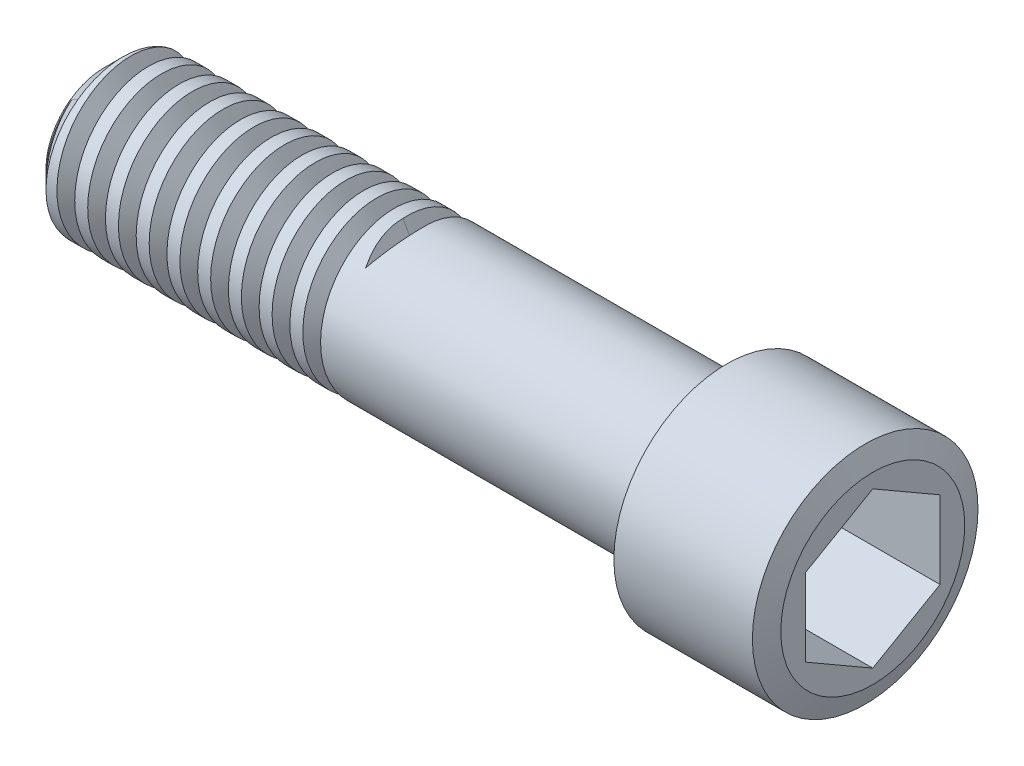
SolidWorks part; units mm, degrees
material "Cast Carbon Steel"
ref_plane "Front Plane" through (0, 0, 0) normal (0, 0, 1) x (1, 0, 0)
ref_plane "Top Plane" through (0, 0, 0) normal (0, 1, 0) x (1, 0, 0)
ref_plane "Right Plane" through (0, 0, 0) normal (1, 0, 0) x (0, 0, -1)
sketch "Sketch1" plane through (0, 0, 0) normal (0, 0, 1) x (1, 0, 0)
  line L0 (15.875, 0) -> (-15.875, 0) construction
  line L1 (-15.875, 0) -> (-15.875, 2.413)
  line L2 (-15.113, 3.175) -> (9.525, 3.175)
  line L3 (9.525, 3.175) -> (9.525, 5.5562)
  line L4 (9.8379, 6.4158) -> (15.5621, 6.4158)
  line L5 (15.875, 5.5562) -> (15.875, 0)
  line L6 (9.525, 5.5562) -> (9.8379, 6.4158)
  line L7 (15.5621, 6.4158) -> (15.875, 5.5562)
  line L8 (-15.875, 2.413) -> (-15.113, 3.175)
  line L9 (13.0969, 4.8119) -> (15.875, 6.4158) construction
  line L10 (15.875, 6.4158) -> (18.6531, 4.8119) construction
  line L11 (-15.875, 0) -> (15.875, 0)
  circle A0 centre (15.875, 0) radius 5.5563 construction
  point P4 (0, 0)
  point P5 (-15.875, 3.175)
  dimension "D8" = 11.1125
  dimension "D1" = 25.4
  dimension "D2" = 20
  dimension "D3" = 20
  dimension "D4" = 6.35
  dimension "D5" = 6.35
  dimension "D6" = 60
revolve "Revolve1" add sketch "Sketch1" angle 360 about L11
sketch "Sketch2" plane through (15.875, 0, 0) normal (1, 0, 0) x (0, 0, -1)
  line L1 (0, 6.4158) -> (-5.5562, 3.2079)
  line L2 (-5.5562, 3.2079) -> (-5.5562, -3.2079)
  line L3 (-5.5562, -3.2079) -> (0, -6.4158)
  line L4 (0, -6.4158) -> (5.5562, -3.2079)
  line L5 (5.5562, -3.2079) -> (5.5562, 3.2079)
  line L6 (5.5562, 3.2079) -> (0, 6.4158)
  circle A0 centre (0, 0) radius 5.5562 construction
  circle A1 centre (0, 0) radius 5.5563 construction
extrude "Cut-Extrude1" [suppressed] cut sketch "Sketch2" against normal through all flip side to cut
sketch "Sketch6" plane through (0, 0, 0) normal (0, 0, 1) x (1, 0, 0)
  line L0 (9.525, 0) -> (15.875, 0) construction
  line L1 (9.525, 3.175) -> (9.525, -3.175) construction
  line L2 (15.875, -5.5563) -> (15.875, 5.5562) construction
  line L3 (9.525, 3.8013) -> (9.8379, 4.6609)
  line L4 (9.525, 5.5562) -> (9.525, -5.5563) construction
  line L5 (9.8379, -6.4158) -> (9.8379, 6.4158) construction
  line L6 (9.8379, 4.6609) -> (15.5621, 4.6609)
  line L7 (15.5621, -6.4158) -> (15.5621, 6.4158) construction
  line L8 (15.5621, 4.6609) -> (15.875, 3.8013)
  line L9 (15.875, 3.8013) -> (15.875, 6.4158)
  line L10 (15.875, 6.4158) -> (9.525, 6.4158)
  line L11 (9.525, 6.4158) -> (9.525, 3.8013)
  line L12 (9.8379, 6.4158) -> (9.525, 5.5562) construction
  line L13 (15.875, 5.5562) -> (15.5621, 6.4158) construction
  line L14 (15.5621, 6.4158) -> (9.8379, 6.4158) construction
  dimension "D1" = 9.3218
revolve "Cut-Revolve1" cut sketch "Sketch6" angle 360 about L0
sketch "Sketch3" plane through (-15.875, 0, 0) normal (-1, 0, 0) x (0, 0, 1)
  circle A0 centre (0, 0) radius 3.175 construction
  circle A1 centre (0, 0) radius 3.175
curve "Helix/Spiral1" pitch 1.27 height 12.7 radius 3.175 centre (-15.875, 0, 0) axis (1, 0, 0) start towards (0, 1, 0)
sketch "Sketch4" plane through (0, 0, 0) normal (0, 0, 1) x (1, 0, 0)
  line L0 (-16.2416, 3.175) -> (-15.5084, 3.175)
  line L1 (-15.5084, 3.175) -> (-15.875, 2.54)
  line L2 (-15.875, 2.54) -> (-16.2416, 3.175)
  line L3 (-15.875, 0) -> (6.1656, 0) construction
  line L4 (-15.875, 2.413) -> (-15.875, -2.413) construction
  line L5 (9.525, 3.175) -> (-15.113, 3.175) construction
  dimension "D1" = 60
  dimension "D2" = 5.08
sweep "Cut-Sweep1" cut profiles "Sketch4" path "Helix/Spiral1" align with end faces yes
sketch "Sketch5" plane through (0, 0, 0) normal (0, 0, -1) x (-1, 0, 0)
  line L3 (2.8084, 3.175) -> (3.175, 2.54)
  line L4 (3.175, 2.54) -> (3.5416, 3.175)
  line L5 (3.5416, 3.175) -> (2.8084, 3.175)
  line L6 (2.8084, 3.175) -> (3.175, 2.54)
  line L7 (3.175, 2.54) -> (3.5416, 3.175)
  line L8 (3.5416, 3.175) -> (2.8084, 3.175)
  dimension "D1" = 0
extrude "Cut-Extrude2" cut sketch "Sketch5" against normal through all
sketch "Sketch7" plane through (15.875, 0, 0) normal (1, 0, 0) x (0, 0, -1)
  line L1 (0, -3.2079) -> (2.7781, -1.604)
  line L2 (2.7781, -1.604) -> (2.7781, 1.604)
  line L3 (2.7781, 1.604) -> (0, 3.2079)
  line L4 (0, 3.2079) -> (-2.7781, 1.604)
  line L5 (-2.7781, 1.604) -> (-2.7781, -1.604)
  line L6 (-2.7781, -1.604) -> (0, -3.2079)
  circle A0 centre (0, 0) radius 2.7781 construction
  dimension "D1" = 5.5562
extrude "Cut-Extrude3" cut sketch "Sketch7" against normal blind 4.7625
